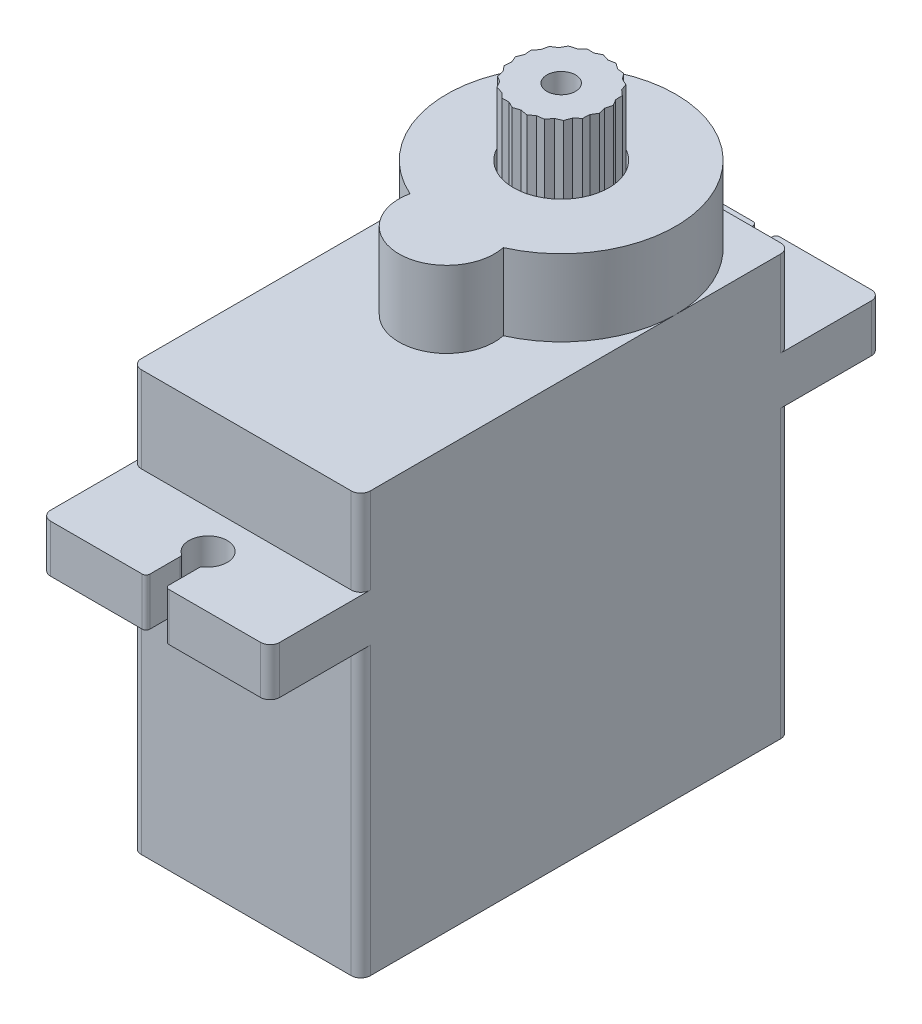
SolidWorks part; units mm, degrees
ref_plane "Ön Düzlem" through (0, 0, 0) normal (0, 0, 1) x (1, 0, 0)
ref_plane "Üst Düzlem" through (0, 0, 0) normal (0, 1, 0) x (1, 0, 0)
ref_plane "Sağ Düzlem" through (0, 0, 0) normal (1, 0, 0) x (0, 0, -1)
sketch "Çizim1" plane through (0, 0, 0) normal (0, 1, 0) x (1, 0, 0)
  line L1 (-5.5, 11.25) -> (5.5, 11.25)
  line L2 (-6, 10.75) -> (-6, -10.75)
  line L3 (-5.5, -11.25) -> (5.5, -11.25)
  line L4 (6, 10.75) -> (6, -10.75)
  line L5 (-6, 11.25) -> (6, -11.25) construction
  line L6 (-6, -11.25) -> (6, 11.25) construction
  arc A0 (5.5, -11.25) -> (6, -10.75) centre (5.5, -10.75) ccw
  arc A1 (-6, -10.75) -> (-5.5, -11.25) centre (-5.5, -10.75) ccw
  arc A2 (5.5, 11.25) -> (6, 10.75) centre (5.5, 10.75) cw
  arc A3 (-5.5, 11.25) -> (-6, 10.75) centre (-5.5, 10.75) ccw
  point P0 (0, 0)
  dimension "D3" = 0.5
  dimension "D1" = 12
  dimension "D2" = 22.5
extrude "Yükseklik-Ekstrüzyon1" add sketch "Çizim1" along normal blind 1
sketch "Çizim2" plane through (0, 1, 0) normal (0, 1, 0) x (1, 0, 0)
  line L0 (-5, 9.25) -> (-5, -9.25)
  line L1 (-5.5, 11.25) -> (5.5, 11.25)
  line L2 (-6, 10.75) -> (-6, -10.75)
  line L3 (-5.5, -11.25) -> (5.5, -11.25)
  line L4 (6, 10.75) -> (6, -10.75)
  line L5 (-6, 11.25) -> (-5.8961, 11.0552) construction
  line L6 (-6, -11.25) -> (-5.8961, -11.0552) construction
  line L7 (-4, -10.25) -> (4, -10.25)
  line L8 (5, 9.25) -> (5, -9.25)
  line L9 (-4, 10.25) -> (4, 10.25)
  line L10 (-6, -11.25) -> (6, -11.25) construction
  line L11 (6, 11.25) -> (6, -11.25) construction
  line L12 (-6, 11.25) -> (-6, -11.25) construction
  line L13 (-6, 11.25) -> (6, 11.25) construction
  line L14 (-5, 10.25) -> (5, 10.25) construction
  line L15 (-5, 10.25) -> (-5, -10.25) construction
  line L16 (-4.9345, 9.2521) -> (4.9345, -9.2521) construction
  line L17 (5, 10.25) -> (5, -10.25) construction
  line L18 (5.8961, 11.0552) -> (6, 11.25) construction
  line L19 (-5, -10.25) -> (5, -10.25) construction
  line L20 (5.8961, -11.0552) -> (6, -11.25) construction
  line L21 (-4.9345, -9.2521) -> (4.9345, 9.2521) construction
  arc A0 (5.5, -11.25) -> (6, -10.75) centre (5.5, -10.75) ccw
  arc A1 (-6, -10.75) -> (-5.5, -11.25) centre (-5.5, -10.75) ccw
  arc A2 (5.5, 11.25) -> (6, 10.75) centre (5.5, 10.75) cw
  arc A3 (-5.5, 11.25) -> (-6, 10.75) centre (-5.5, 10.75) ccw
  arc A5 (4, 10.25) -> (5, 9.25) centre (5, 10.25) ccw
  arc A7 (-4, -10.25) -> (-5, -9.25) centre (-5, -10.25) ccw
  arc A8 (-5, 9.25) -> (-4, 10.25) centre (-5, 10.25) ccw
  arc A9 (5, -9.25) -> (4, -10.25) centre (5, -10.25) ccw
  point P0 (0, 0)
  dimension "D2" = 0.5
  dimension "D1" = 1
extrude "Yükseklik-Ekstrüzyon2" add sketch "Çizim2" along normal blind 5
sketch "Çizim3" plane through (0, 6, 0) normal (0, 1, 0) x (1, 0, 0)
  line L0 (0, -10.25) -> (0, -11.25) construction
  line L1 (-4, -10.25) -> (4, -10.25) construction
  line L2 (-5.5, -11.25) -> (5.5, -11.25) construction
  line L3 (0, -11.25) -> (0, -10.75) construction
  line L4 (0, -10.75) -> (2.4368, -10.75) construction
  line L6 (-2, -10.25) -> (2, -10.25)
  line L7 (-2, -10.25) -> (-2, -11.25)
  line L8 (-2, -11.25) -> (2, -11.25)
  line L9 (2, -10.25) -> (2, -11.25)
  line L10 (-2, -10.25) -> (2, -11.25) construction
  line L11 (-2, -11.25) -> (2, -10.25) construction
  dimension "D1" = 4
extrude "Kes-Ekstrüzyon1" cut sketch "Çizim3" against normal blind 1
fillet "Radyus1" radius 0.1 2 edges at (2, 5, 10.75) (-2, 5, 10.75)
sketch "Çizim4" plane through (0, 6, 0) normal (0, 1, 0) x (1, 0, 0)
  line L0 (-4, 10.25) -> (4, 10.25)
  line L1 (-5.5, 11.25) -> (5.5, 11.25)
  line L2 (-6, 10.75) -> (-6, -10.75)
  line L3 (-5.5, -11.25) -> (5.5, -11.25)
  line L4 (6, 10.75) -> (6, -10.75)
  line L5 (-6, 11.25) -> (-5.8961, 11.0552) construction
  line L6 (-6, -11.25) -> (-5.8961, -11.0552) construction
  line L7 (-4, 10.25) -> (4, 10.25)
  line L8 (5, 9.25) -> (5, -9.25)
  line L9 (5, -9.25) -> (5, 9.25)
  line L10 (-4, 10.25) -> (4, 10.25)
  line L11 (5, 9.25) -> (5, -9.25)
  line L12 (-4, -10.25) -> (4, -10.25)
  line L13 (-5, 9.25) -> (-5, -9.25)
  line L14 (-4.9345, 9.2521) -> (4.9345, -9.2521) construction
  line L15 (-5, 10.25) -> (-5, -10.25) construction
  line L16 (-5, 10.25) -> (5, 10.25) construction
  line L17 (5, 10.25) -> (5, -10.25) construction
  line L18 (5.8961, 11.0552) -> (6, 11.25) construction
  line L19 (5.8961, -11.0552) -> (6, -11.25) construction
  line L20 (-5, -10.25) -> (5, -10.25) construction
  line L21 (-4.9345, -9.2521) -> (4.9345, 9.2521) construction
  arc A0 (5.5, -11.25) -> (6, -10.75) centre (5.5, -10.75) ccw
  arc A1 (-6, -10.75) -> (-5.5, -11.25) centre (-5.5, -10.75) ccw
  arc A2 (5.5, 11.25) -> (6, 10.75) centre (5.5, 10.75) cw
  arc A3 (-5.5, 11.25) -> (-6, 10.75) centre (-5.5, 10.75) ccw
  arc A4 (-5, 9.25) -> (-4, 10.25) centre (-5, 10.25) ccw
  arc A5 (4, 10.25) -> (5, 9.25) centre (5, 10.25) ccw
  arc A6 (-4, -10.25) -> (-5, -9.25) centre (-5, -10.25) ccw
  arc A7 (5, -9.25) -> (4, -10.25) centre (5, -10.25) ccw
  arc A8 (5, 10.25) -> (5, 10.25) centre (5, 10.25) cw
  arc A9 (5, -10.25) -> (5, -10.25) centre (5, -10.25) ccw
  arc A10 (-5, -10.25) -> (-5, -10.25) centre (-5, -10.25) ccw
  arc A11 (-5, 10.25) -> (-5, 10.25) centre (-5, 10.25) ccw
  point P0 (0, 0)
  line M12 (4, -10.25) -> (2, -10.25)
  line M14 (2, -11.25) -> (5.5, -11.25)
  arc M15 (5.5, -11.25) -> (6, -10.75) centre (5.5, -10.75) ccw
  line M16 (6, -10.75) -> (6, 10.75)
  arc M17 (6, 10.75) -> (5.5, 11.25) centre (5.5, 10.75) ccw
  line M18 (5.5, 11.25) -> (-5.5, 11.25)
  arc M19 (-5.5, 11.25) -> (-6, 10.75) centre (-5.5, 10.75) ccw
  line M20 (-6, 10.75) -> (-6, -10.75)
  arc M21 (-6, -10.75) -> (-5.5, -11.25) centre (-5.5, -10.75) ccw
  line M22 (-5.5, -11.25) -> (-2, -11.25)
  line M24 (-2, -10.25) -> (-4, -10.25)
  arc M25 (-4, -10.25) -> (-5, -9.25) centre (-5, -10.25) ccw
  line M26 (-5, -9.25) -> (-5, 9.25)
  arc M27 (-5, 9.25) -> (-4, 10.25) centre (-5, 10.25) ccw
  line M28 (-4, 10.25) -> (4, 10.25)
  arc M29 (4, 10.25) -> (5, 9.25) centre (5, 10.25) ccw
  line M30 (5, 9.25) -> (5, -9.25)
  arc M31 (5, -9.25) -> (4, -10.25) centre (5, -10.25) ccw
  dimension "D1" = 0.5
  dimension "D2" = 1
extrude "Yükseklik-Ekstrüzyon4" add sketch "Çizim4" along normal blind 9 contours M31 M12 M14 M15 M16 M17 M18 M19 M20 M21 M22 M24 M25 M26 M27 M28 M29 M30 | L12 L3 region at (0, 6, -10.995)
sketch "Çizim6" plane through (0, 15, 0) normal (0, 1, 0) x (1, 0, 0)
  line L0 (0, -10.25) -> (0, -12.25) construction
  line L1 (-5.5, 16) -> (-0.7, 16)
  line L2 (-6, 15.5) -> (-6, -15.5)
  line L3 (-5.5, -16) -> (-0.7, -16)
  line L4 (6, 15.5) -> (6, -15.5)
  line L5 (-6, 16) -> (6, -16) construction
  line L6 (-3.8437, -10.25) -> (6, 16) construction
  line L7 (-4, 10.25) -> (4, 10.25)
  line L8 (-5, 9.25) -> (-5, -9.25)
  line L9 (-4, -10.25) -> (4, -10.25)
  line L10 (5, 9.25) -> (5, -9.25)
  line L11 (-4.5616, 9.3512) -> (4.5616, -9.3512) construction
  line L12 (-4.5616, -9.3512) -> (4.5616, 9.3512) construction
  line L13 (0, -12.25) -> (0, -11.25) construction
  line L14 (-5.5, -11.25) -> (5.5, -11.25) construction
  line L15 (0, -11.25) -> (8.7476, -11.25) construction
  line L16 (0, -12.25) -> (8.7476, -12.25) construction
  line L17 (0.7, -16) -> (5.5, -16)
  line L18 (-0.5, -14.2247) -> (-0.5, -15.8)
  line L19 (0.5, -14.2247) -> (0.5, -15.8)
  line L20 (0, 0) -> (5, 0) construction
  line L21 (0.5, 14.2247) -> (0.5, 15.8)
  line L22 (-0.5, 14.2247) -> (-0.5, 15.8)
  line L23 (0.7, 16) -> (5.5, 16)
  arc A0 (-5, 9.25) -> (-4, 10.25) centre (-5, 10.25) ccw
  arc A1 (4, 10.25) -> (5, 9.25) centre (5, 10.25) ccw
  arc A2 (5, -9.25) -> (4, -10.25) centre (5, -10.25) ccw
  arc A3 (-4, -10.25) -> (-5, -9.25) centre (-5, -10.25) ccw
  arc A4 (5.5, -16) -> (6, -15.5) centre (5.5, -15.5) ccw
  arc A5 (-6, -15.5) -> (-5.5, -16) centre (-5.5, -15.5) ccw
  arc A6 (5.5, 16) -> (6, 15.5) centre (5.5, 15.5) cw
  arc A7 (-5.5, 16) -> (-6, 15.5) centre (-5.5, 15.5) ccw
  arc A9 (0.5833, -14.0622) -> (-0.5833, -14.0622) centre (0, -13.25) ccw
  arc A10 (0.5, -14.2247) -> (0.5833, -14.0622) centre (0.7, -14.2247) cw
  arc A11 (-0.5, -14.2247) -> (-0.5833, -14.0622) centre (-0.7, -14.2247) ccw
  arc A12 (0.5, -15.8) -> (0.7, -16) centre (0.7, -15.8) ccw
  arc A13 (-0.5, -15.8) -> (-0.7, -16) centre (-0.7, -15.8) cw
  arc A14 (0.5, 15.8) -> (0.7, 16) centre (0.7, 15.8) cw
  arc A15 (-0.5, 15.8) -> (-0.7, 16) centre (-0.7, 15.8) ccw
  arc A16 (0.5, 14.2247) -> (0.5833, 14.0622) centre (0.7, 14.2247) ccw
  arc A17 (-0.5, 14.2247) -> (-0.5833, 14.0622) centre (-0.7, 14.2247) cw
  arc A18 (0.5833, 14.0622) -> (-0.5833, 14.0622) centre (0, 13.25) cw
  point P0 (0, 0)
  point P6 (0, 0)
  point P54 (0.5, -16)
  dimension "D2" = 0.5
  dimension "D4" = 2
  dimension "D5" = 0.2
  dimension "D1" = 32
  dimension "D3" = 1
extrude "Yükseklik-Ekstrüzyon5" add sketch "Çizim6" along normal blind 2.5
sketch "Çizim7" plane through (0, 17.5, 0) normal (0, 1, 0) x (1, 0, 0)
  line L0 (6, -15.5) -> (6, 15.5) construction
  line L1 (-5.5, 11.25) -> (5.5, 11.25)
  line L2 (-6, 10.75) -> (-6, -10.75)
  line L3 (-5.5, -11.25) -> (5.5, -11.25)
  line L4 (6, 10.75) -> (6, -10.75)
  line L5 (-6, 11.25) -> (-5.8961, 11.0552) construction
  line L6 (-6, -11.25) -> (-5.8961, -11.0552) construction
  line L7 (-5, 9.25) -> (-5, -9.25)
  line L8 (-4, 10.25) -> (4, 10.25)
  line L9 (5, 9.25) -> (5, -9.25)
  line L10 (4, -10.25) -> (-4, -10.25)
  line L12 (-4.9345, 9.2521) -> (4.9345, -9.2521) construction
  line L13 (5.8961, 11.0552) -> (6, 11.25) construction
  line L14 (5.8961, -11.0552) -> (6, -11.25) construction
  line L15 (-5, -9.25) -> (-5, 9.25)
  line L16 (-4.9345, -9.2521) -> (4.9345, 9.2521) construction
  line L17 (-5, 9.25) -> (-5, -9.25)
  arc A0 (-6, -10.75) -> (-5.5, -11.25) centre (-5.5, -10.75) ccw
  arc A1 (5.5, -11.25) -> (6, -10.75) centre (5.5, -10.75) ccw
  arc A2 (5.5, 11.25) -> (6, 10.75) centre (5.5, 10.75) cw
  arc A3 (-5.5, 11.25) -> (-6, 10.75) centre (-5.5, 10.75) ccw
  arc A4 (-5, 9.25) -> (-4, 10.25) centre (-5, 10.25) ccw
  arc A5 (4, 10.25) -> (5, 9.25) centre (5, 10.25) ccw
  arc A6 (5, -9.25) -> (4, -10.25) centre (5, -10.25) ccw
  arc A8 (-4, -10.25) -> (-5, -9.25) centre (-5, -10.25) ccw
  point P0 (0, 0)
  line M16 (6, -15.5) -> (6, 15.5)
  line M28 (-6, 15.5) -> (-6, -15.5)
  line M39 (-5, -9.25) -> (-5, 9.25)
  arc M40 (-5, 9.25) -> (-4, 10.25) centre (-5, 10.25) ccw
  line M41 (-4, 10.25) -> (4, 10.25)
  arc M42 (4, 10.25) -> (5, 9.25) centre (5, 10.25) ccw
  line M43 (5, 9.25) -> (5, -9.25)
  arc M44 (5, -9.25) -> (4, -10.25) centre (5, -10.25) ccw
  line M45 (4, -10.25) -> (-4, -10.25)
  arc M46 (-4, -10.25) -> (-5, -9.25) centre (-5, -10.25) ccw
  dimension "D2" = 0.5
  dimension "D1" = 22.5
extrude "Yükseklik-Ekstrüzyon6" add sketch "Çizim7" along normal blind 3.5 contours L1 A3 A0 L3 A1 A2 M28 M16 M46 M39 M40 M41 M42 M43 M44 M45 region at (0, 17.5, -10.995)
sketch "Çizim8" plane through (0, 21, 0) normal (0, 1, 0) x (1, 0, 0)
  line L0 (6, -15.5) -> (6, -10.75) construction
  line L1 (-5.5, 11.25) -> (5.5, 11.25)
  line L2 (-6, 10.75) -> (-6, -10.75)
  line L3 (-5.5, -11.25) -> (5.5, -11.25)
  line L4 (6, 10.75) -> (6, -10.75)
  line L5 (-6, 11.25) -> (6, -11.25) construction
  line L6 (-6, -11.25) -> (6, 11.25) construction
  arc A0 (-6, -10.75) -> (-5.5, -11.25) centre (-5.5, -10.75) ccw
  arc A1 (5.5, -11.25) -> (6, -10.75) centre (5.5, -10.75) ccw
  arc A2 (5.5, 11.25) -> (6, 10.75) centre (5.5, 10.75) cw
  arc A3 (-5.5, 11.25) -> (-6, 10.75) centre (-5.5, 10.75) ccw
  point P0 (0, 0)
  dimension "D1" = 0.5
extrude "Yükseklik-Ekstrüzyon7" add sketch "Çizim8" along normal blind 1
sketch "Çizim9" plane through (0, 22, 0) normal (0, 1, 0) x (1, 0, 0)
  line L0 (-6, 5.25) -> (6, 5.25) construction
  line L1 (-6, 10.75) -> (-6, -10.75) construction
  line L2 (6, -10.75) -> (6, 10.75) construction
  line L3 (5.5, 11.25) -> (-5.5, 11.25) construction
  line L4 (0, 5.25) -> (0, -0.75) construction
  arc A0 (2.4451, -0.2292) -> (-2.4451, -0.2292) centre (0, 5.25) ccw
  arc A1 (-2.4451, -0.2292) -> (2.4451, -0.2292) centre (0, -0.75) ccw
  arc A2 (1.0153, 0.3542) -> (-1.0153, 0.3542) centre (0, 5.25) ccw
  arc A3 (-1.0153, 0.3542) -> (1.0153, 0.3542) centre (0, -0.75) ccw
  dimension "D2" = 5
  dimension "D1" = 6
  dimension "D3" = 1
extrude "Kes-Ekstrüzyon2" cut sketch "Çizim9" against normal blind 1 contours A2 A3
extrude "Yükseklik-Ekstrüzyon8" add sketch "Çizim9<3>" along normal blind 3
sketch "Çizim9<3>" plane through (0, 22, 0) normal (0, 1, 0) x (1, 0, 0) same geometry as "Çizim9"
fillet "Radyus2" radius 0.5 2 edges at (1.0153, 23, -0.3542) (-1.0153, 23, -0.3542)
sketch "Çizim10" plane through (0, 25, 0) normal (0, 1, 0) x (1, 0, 0)
  arc A0 (2.4451, -0.2292) -> (-2.4451, -0.2292) centre (0, 5.25) ccw
  arc A1 (-2.4451, -0.2292) -> (2.4451, -0.2292) centre (0, -0.75) ccw
extrude "Yükseklik-Ekstrüzyon9" add sketch "Çizim10" along normal blind 1
sketch "Çizim11" plane through (0, 26, 0) normal (0, 1, 0) x (1, 0, 0)
  circle A0 centre (0, 5.25) radius 2.5
  dimension "D1" = 5
extrude "Kes-Ekstrüzyon3" cut sketch "Çizim11" against normal blind 10
sketch "Çizim15" plane through (0, 26, 0) normal (0, 1, 0) x (1, 0, 0)
  circle A0 centre (0, -0.75) radius 0.25
  dimension "D1" = 0.5
extrude "Yükseklik-Ekstrüzyon12" add sketch "Çizim15" against normal blind 11
ref_plane "Düzlem3" through (0, 30, 0) normal (0, 1, 0) x (1, 0, 0)
sketch "Çizim19" plane through (0, 30, 0) normal (0, 1, 0) x (1, 0, 0)
  circle A0 centre (0, 5.25) radius 2.4
  dimension "D1" = 4.8
extrude "Yükseklik-Ekstrüzyon17" add sketch "Çizim19" against normal blind 5 separate body
sketch "Çizim20" plane through (0, 25, 0) normal (0, -1, 0) x (1, 0, 0)
  circle A0 centre (0, -5.25) radius 4.75
  dimension "D1" = 9.5
extrude "Yükseklik-Ekstrüzyon18" add sketch "Çizim20" along normal blind 3
sketch "Çizim21" plane through (0, 30, 0) normal (0, 1, 0) x (1, 0, 0)
  circle A0 centre (0, 5.25) radius 0.75
  dimension "D1" = 1.5
extrude "Kes-Ekstrüzyon5" cut sketch "Çizim21" against normal blind 10
ref_plane "Düzlem4" through (0, 25.5, 0) normal (0, 1, 0) x (1, 0, 0)
sketch "Çizim22" plane through (0, 25.5, 0) normal (0, 1, 0) x (1, 0, 0)
  line L0 (0, 11.25) -> (0, -3.25) construction
  arc A0 (2.4451, -0.2292) -> (-2.4451, -0.2292) centre (0, 5.25) ccw construction
  arc A1 (-2.4451, -0.2292) -> (2.4451, -0.2292) centre (0, -0.75) ccw construction
  circle A2 centre (0, -0.75) radius 0.5
  dimension "D1" = 1
extrude "Yükseklik-Ekstrüzyon19" add sketch "Çizim22" against normal blind 5
sketch "Çizim23" plane through (0, 20.5, 0) normal (0, -1, 0) x (1, 0, 0)
  circle A0 centre (0, 0.75) radius 4
  dimension "D1" = 8
extrude "Yükseklik-Ekstrüzyon20" add sketch "Çizim23" along normal blind 2
sketch "Çizim24" plane through (0, 22, 0) normal (0, -1, 0) x (1, 0, 0)
  circle A0 centre (0, -5.25) radius 0.75
extrude "Yükseklik-Ekstrüzyon21" add sketch "Çizim24" along normal blind 7 separate body
ref_plane "Düzlem5" through (0, 19, 0) normal (0, -1, 0) x (-1, 0, 0)
sketch "Çizim25" plane through (0, 19, 0) normal (0, -1, 0) x (-1, 0, 0)
  circle A0 centre (0, 5.25) radius 3.5
  dimension "D1" = 7
extrude "Yükseklik-Ekstrüzyon22" add sketch "Çizim25" along normal blind 1
ref_plane "Düzlem6" through (0, 17.5, 0) normal (0, -1, 0) x (-1, 0, 0)
sketch "Çizim26" plane through (0, 17.5, 0) normal (0, -1, 0) x (-1, 0, 0)
  circle A0 centre (0, -0.75) radius 4.5
  dimension "D1" = 9
extrude "Yükseklik-Ekstrüzyon23" add sketch "Çizim26" along normal blind 1
sketch "Çizim32" plane through (0, 0, 10.25) normal (0, 0, -1) x (-1, 0, 0)
  line L1 (2, 6) -> (-2, 6)
  line L2 (2, 6) -> (2, 5.1)
  line L3 (1.9, 5) -> (-1.9, 5)
  line L4 (-2, 6) -> (-2, 5.1)
  arc A0 (-1.9, 5) -> (-2, 5.1) centre (-1.9, 5.1) cw
  arc A1 (2, 5.1) -> (1.9, 5) centre (1.9, 5.1) cw
  point P7 (-2, 5)
  dimension "D3" = 0.1
  dimension "D1" = 1
  dimension "D2" = 4
extrude "Kes-Ekstrüzyon7" cut sketch "Çizim32" along normal blind 30
sketch "Çizim33" plane through (0, 0, 11.25) normal (0, 0, 1) x (1, 0, 0)
  line L1 (-2, 6) -> (2, 6)
  line L2 (-2, 6) -> (-2, 5.1)
  line L3 (-1.9, 5) -> (1.9, 5)
  line L4 (2, 6) -> (2, 5.1)
  arc A0 (1.9, 5) -> (2, 5.1) centre (1.9, 5.1) ccw
  arc A1 (-2, 5.1) -> (-1.9, 5) centre (-1.9, 5.1) ccw
  point P7 (2, 5)
  point P10 (-2, 5)
  dimension "D3" = 0.1
  dimension "D1" = 1
  dimension "D2" = 4
extrude "Yükseklik-Ekstrüzyon33" add sketch "Çizim33" against normal blind 1
sketch "Çizim34" plane through (0, 1, 0) normal (0, 1, 0) x (1, 0, 0)
  line L0 (-5, -6.25) -> (5, -6.25) construction
  line L1 (-5, 9.25) -> (-5, -9.25) construction
  line L2 (5, -9.25) -> (5, 9.25) construction
  line L3 (-4, -10.25) -> (4, -10.25) construction
  line L5 (-3, -3.25) -> (3, -3.25)
  line L6 (-4, -4.25) -> (-4, -8.25)
  line L7 (-3, -9.25) -> (3, -9.25)
  line L8 (4, -4.25) -> (4, -8.25)
  line L9 (-4, -3.25) -> (4, -9.25) construction
  line L10 (-4, -9.25) -> (4, -3.25) construction
  arc A0 (3, -9.25) -> (4, -8.25) centre (3, -8.25) ccw
  arc A1 (-4, -8.25) -> (-3, -9.25) centre (-3, -8.25) ccw
  arc A2 (3, -3.25) -> (4, -4.25) centre (3, -4.25) cw
  arc A3 (-3, -3.25) -> (-4, -4.25) centre (-3, -4.25) ccw
  point P8 (0, -6.25)
  dimension "D4" = 1
  dimension "D1" = 4
  dimension "D2" = 6
  dimension "D3" = 8
extrude "Yükseklik-Ekstrüzyon34" add sketch "Çizim34" along normal blind 14
ref_plane "Düzlem8" through (0, 1, 0) normal (0, -1, 0) x (-1, 0, 0)
sketch "Çizim37" plane through (0, 1, 0) normal (0, -1, 0) x (-1, 0, 0)
  line L0 (4, -6.25) -> (-4, -6.25) construction
  line L1 (4, -4.25) -> (4, -8.25) construction
  line L2 (-4, -8.25) -> (-4, -4.25) construction
  line L4 (4, -9.25) -> (-4, -9.25)
  line L5 (4, -9.25) -> (4, -3.25)
  line L6 (4, -3.25) -> (-4, -3.25)
  line L7 (-4, -9.25) -> (-4, -3.25)
  line L8 (4, -9.25) -> (-4, -3.25) construction
  line L9 (4, -3.25) -> (-4, -9.25) construction
  point P6 (0, -6.25)
  dimension "D1" = 6
  dimension "D2" = 8
extrude "Yükseklik-Ekstrüzyon36" add sketch "Çizim37" against normal blind 1
ref_plane "Düzlem9" through (0, 0, -10.75) normal (0, 0, -1) x (-1, 0, 0)
sketch "Çizim39" plane through (0, 0, -10.75) normal (0, 0, -1) x (-1, 0, 0)
  line L0 (0, 0) -> (0, 6.0146) construction
  line L1 (-5.5, 0) -> (5.5, 0) construction
  line L2 (-2, 6.0146) -> (2, 6.0146)
  line L4 (-2, 6.0146) -> (-2, 5.0146)
  line L5 (-2, 5.0146) -> (2, 5.0146)
  line L6 (2, 6.0146) -> (2, 5.0146)
  line L7 (0, 6.0146) -> (2, 5.0146) construction
  line L8 (-2, 5.0146) -> (0, 6.0146) construction
extrude "Yükseklik-Ekstrüzyon37" add sketch "Çizim39" along normal blind 0.1
sketch "Çizim40" plane through (0, 0, -10.85) normal (0, 0, -1) x (-1, 0, 0)
  line L0 (-2, 5.55) -> (2, 5.55) construction
  line L1 (-2, 6) -> (-2, 5.1) construction
  line L2 (2, 5.1) -> (2, 6) construction
  circle A0 centre (0, 5.55) radius 0.4
  circle A1 centre (1, 5.55) radius 0.4
  circle A2 centre (-1, 5.55) radius 0.4
  dimension "D1" = 0.8
  dimension "D2" = 1
  dimension "D3" = 1
extrude "Yükseklik-Ekstrüzyon38" add sketch "Çizim40" along normal blind 2
sketch "Çizim41" plane through (0, 30, 0) normal (0, 1, 0) x (1, 0, 0)
  line L0 (0, 5.25) -> (-2.4, 5.25) construction
  circle A0 centre (0, 5.25) radius 2.4
  circle A1 centre (-2.4, 5.25) radius 0.15
  circle A2 centre (-2.3614, 5.6785) radius 0.15
  circle A3 centre (-2.247, 6.0933) radius 0.15
  circle A4 centre (-2.0603, 6.481) radius 0.15
  circle A5 centre (-1.8074, 6.8291) radius 0.15
  circle A6 centre (-1.4964, 7.1264) radius 0.15
  circle A7 centre (-1.1373, 7.3634) radius 0.15
  circle A8 centre (-0.7416, 7.5325) radius 0.15
  circle A9 centre (-0.3222, 7.6283) radius 0.15
  circle A10 centre (0.1077, 7.6476) radius 0.15
  circle A11 centre (0.5341, 7.5898) radius 0.15
  circle A12 centre (0.9433, 7.4569) radius 0.15
  circle A13 centre (1.3222, 7.253) radius 0.15
  circle A14 centre (1.6586, 6.9847) radius 0.15
  circle A15 centre (1.9416, 6.6607) radius 0.15
  circle A16 centre (2.1623, 6.2913) radius 0.15
  circle A17 centre (2.3135, 5.8885) radius 0.15
  circle A18 centre (2.3903, 5.4651) radius 0.15
  circle A19 centre (2.3903, 5.0349) radius 0.15
  circle A20 centre (2.3135, 4.6115) radius 0.15
  circle A21 centre (2.1623, 4.2087) radius 0.15
  circle A22 centre (1.9416, 3.8393) radius 0.15
  circle A23 centre (1.6586, 3.5153) radius 0.15
  circle A24 centre (1.3222, 3.247) radius 0.15
  circle A25 centre (0.9433, 3.0431) radius 0.15
  circle A26 centre (0.5341, 2.9102) radius 0.15
  circle A27 centre (0.1077, 2.8524) radius 0.15
  circle A28 centre (-0.3222, 2.8717) radius 0.15
  circle A29 centre (-0.7416, 2.9675) radius 0.15
  circle A30 centre (-1.1373, 3.1366) radius 0.15
  circle A31 centre (-1.4964, 3.3736) radius 0.15
  circle A32 centre (-1.8074, 3.6709) radius 0.15
  circle A33 centre (-2.0603, 4.019) radius 0.15
  circle A34 centre (-2.247, 4.4067) radius 0.15
  circle A35 centre (-2.3614, 4.8215) radius 0.15
  circle A36 centre (0, 5.25) radius 2.4 construction
  point P75 (0, 5.25)
  circle M3 centre (0, 5.25) radius 2.4
  dimension "D1" = 0.3
  dimension "D2" = 35
extrude "Kes-Ekstrüzyon8" [suppressed] cut sketch "Çizim41" against normal blind 5 contours A1 A0 M3 | A1 L0 A0 | L0 A1 M3 | A3 | A2 | A35 | A34 | A33 | A32 | A31 | A30 | A29 | A28 | A27 | A26 | A25 | A24 | A23 | A22 | A21 | A20 | A19 | A18 | A17 | A16 | A15 | A14 | A13 | A12 | A11 | A10 | A9 | A8 | A7 | A6 | A5 | A4
sketch "Sketch1" plane through (0, 30, 0) normal (0, 1, 0) x (1, 0, 0)
  line L0 (2.3721, 5.615) -> (2.28, 5.25)
  line L1 (2.28, 5.25) -> (2.3721, 4.885)
  line L2 (2.3721, 5.615) -> (2.4721, 5.615)
  line L3 (2.4721, 5.615) -> (2.4721, 4.885)
  line L4 (2.4721, 4.885) -> (2.3721, 4.885)
  circle A0 centre (0, 5.25) radius 2.4 construction
  circle A1 centre (0, 5.25) radius 2.4 construction
  circle A2 centre (0, 5.25) radius 2.4 construction
  dimension "D1" = 2.28
  dimension "D2" = 0.73
  dimension "D3" = 0.1
extrude "Cut-Extrude1" cut sketch "Sketch1" against normal up to surface (5 mm away) up to face at (0, 25, -2.85)
pattern_circular "CirPattern1" count 21 over 360 about axis through (0, 30, -5.25) along (0, 1, 0) of "Cut-Extrude1"
sketch "Sketch2" plane through (0, 30, 0) normal (0, 1, 0) x (1, 0, 0)
  line L0 (6, 10.75) -> (6, 15.5) construction
  line L1 (-6, -0.75) -> (6, -0.75)
  line L2 (-6, -0.75) -> (-6, 11.25)
  line L3 (-6, 11.25) -> (6, 11.25)
  line L4 (6, -0.75) -> (6, 11.25)
  line L5 (-6, -0.75) -> (6, 11.25) construction
  line L6 (-6, 11.25) -> (6, -0.75) construction
  point P0 (0, 5.25)
  point P6 (6, 11.3218)
extrude "Cut-Extrude2" cut sketch "Sketch2" against normal blind 0.5
